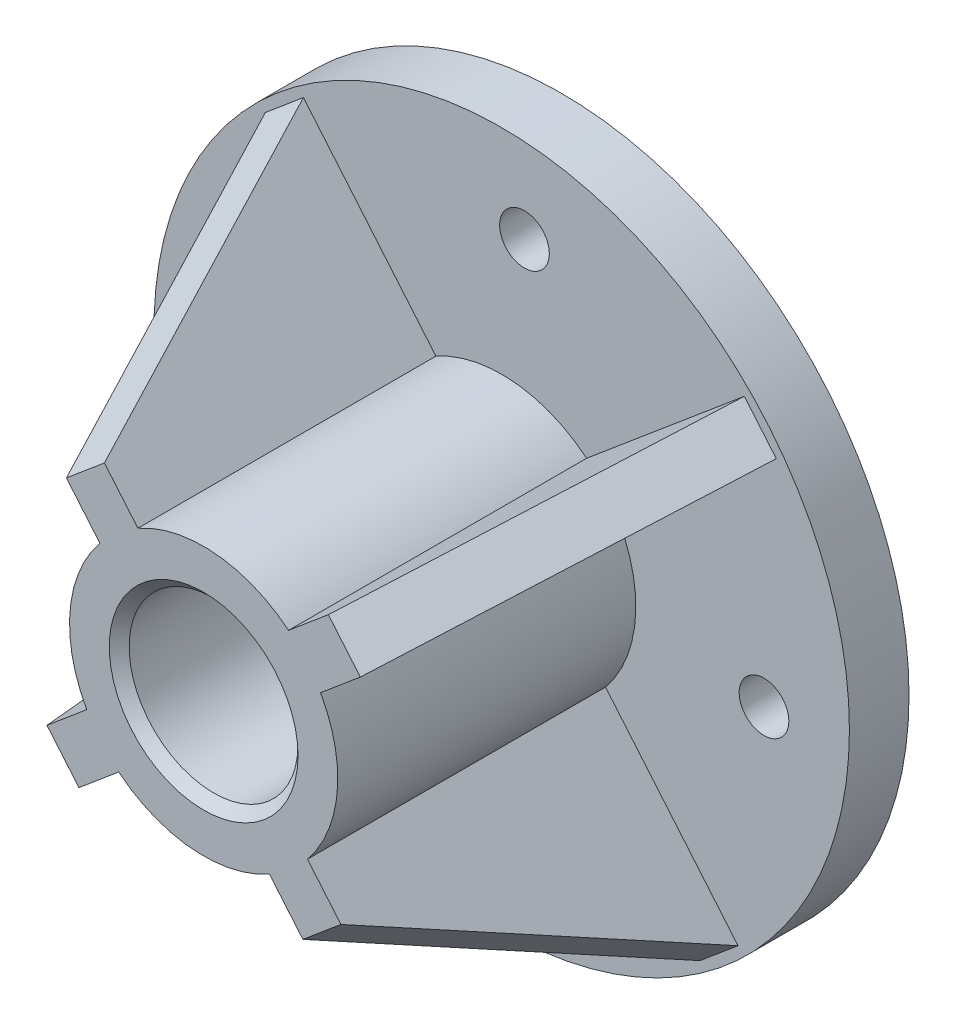
SolidWorks part; units mm, degrees
material "Nylon 6/10"
ref_plane "Front Plane" through (0, 0, 0) normal (0, 0, 1) x (1, 0, 0)
ref_plane "Top Plane" through (0, 0, 0) normal (0, 1, 0) x (1, 0, 0)
ref_plane "Right Plane" through (0, 0, 0) normal (1, 0, 0) x (0, 0, -1)
sketch "Sketch1" plane through (0, 0, 0) normal (0, 0, 1) x (1, 0, 0)
  circle A0 centre (-80.4513, 19.9438) radius 35
  dimension "D1" = 70
extrude "Boss-Extrude1" add sketch "Sketch1" along normal blind 6
sketch "Sketch2" plane through (0, 0, 6) normal (0, 0, 1) x (1, 0, 0)
  circle A0 centre (-80.4513, 19.9438) radius 13.5
  circle A1 centre (-80.4513, 19.9438) radius 8.5
  dimension "D1" = 17
  dimension "D2" = 27
extrude "Boss-Extrude2" add sketch "Sketch2" along normal blind 30
sketch "Sketch3" plane through (0, 0, 6) normal (0, 0, 1) x (1, 0, 0)
  line L0 (-102.9674, 46.7398) -> (-57.9352, -6.8522) construction
  line L1 (-57.9352, -6.8522) -> (-80.4513, 19.9438) construction
  line L2 (-80.4513, 19.9438) -> (-53.6553, 42.4599) construction
  line L3 (-53.6553, 42.4599) -> (-107.2473, -2.5723) construction
  line L4 (-75.0354, 9.6124) -> (-71.2074, 12.8289)
  line L5 (-75.0354, 9.6124) -> (-60.4925, -7.6949)
  line L6 (-71.2074, 12.8289) -> (-56.6645, -4.4783)
  line L7 (-60.4925, -7.6949) -> (-56.6645, -4.4783)
  circle A0 centre (-80.4513, 19.9438) radius 35 construction
  point P10 (-57.9352, -6.8522)
  dimension "D1" = 0
  dimension "D2" = 5
  dimension "D3" = 2.5
  dimension "D4" = 1
extrude "Boss-Extrude3" add sketch "Sketch3" along normal blind 30
chamfer "Chamfer1" distance 30 distance2 15.5 1 edges at (-58.5785, -6.0866, 36) first distance on face at (-58.5785, -6.0866, 21)
pattern_circular "CirPattern2" count 4 over 360 about axis through (-80.4513, 19.9438, 36) along (0, 0, -1) of "Chamfer1", "Boss-Extrude3"
sketch "Sketch4" plane through (0, 0, 6) normal (0, 0, 1) x (1, 0, 0)
  circle A0 centre (-80.4513, 19.9438) radius 8.5
extrude "Cut-Extrude1" cut sketch "Sketch4" against normal blind 30
chamfer "Chamfer2" distance 1 angle 45 1 edges at (-71.9513, 19.9438, 36)
sketch "Sketch5" plane through (0, 0, 6) normal (0, 0, 1) x (1, 0, 0)
  line L0 (-80.4513, 19.9438) -> (-129.867, 24.2327) construction
  line L1 (-104.2381, 44.3659) -> (-90.8999, 28.4923) construction
  arc A0 (-90.8999, 28.4923) -> (-92.2164, 13.3232) centre (-80.4513, 19.9438) ccw construction
  circle A1 centre (-106.8521, 22.2352) radius 2.5
  point P5 (-93.9007, 21.1111)
  point P6 (-110.2227, 22.5277)
  dimension "D3" = 5
  dimension "D1" = 45
  dimension "D2" = 16.3219
  dimension "D4" = 13
extrude "Cut-Extrude2" cut sketch "Sketch5" against normal blind 30
pattern_circular "CirPattern3" count 4 over 360 about axis through (-80.4513, 19.9438, 36) along (0, 0, -1) of "Cut-Extrude2"
